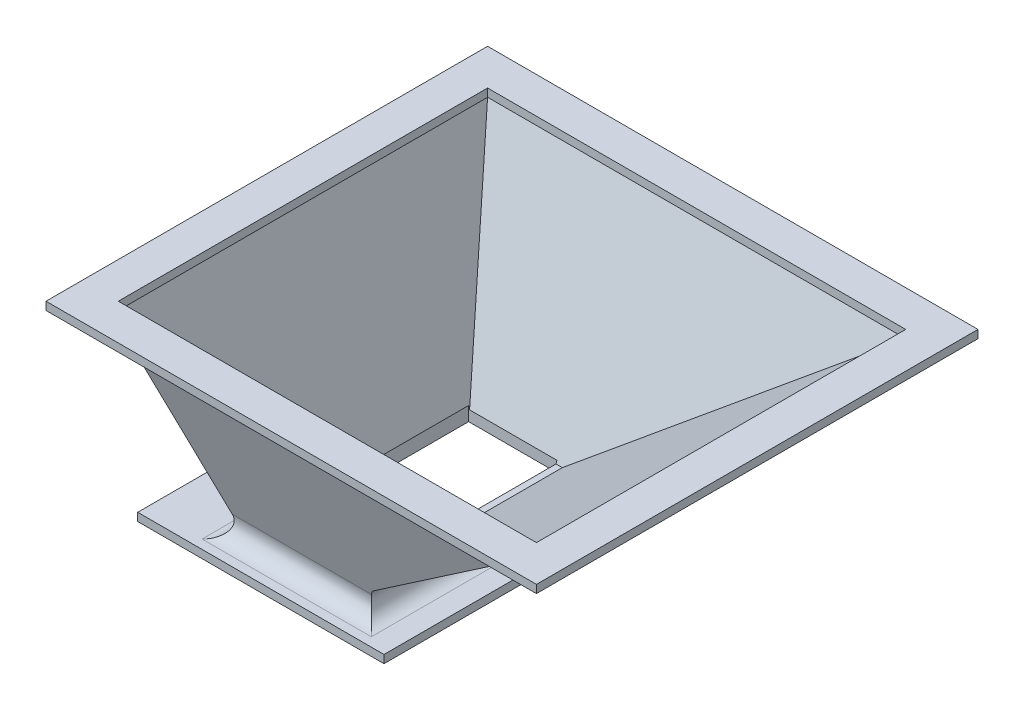
SolidWorks part; units mm, degrees
ref_plane "Front Plane" through (0, 0, 0) normal (0, 0, 1) x (1, 0, 0)
ref_plane "Top Plane" through (0, 0, 0) normal (0, 1, 0) x (1, 0, 0)
ref_plane "Right Plane" through (0, 0, 0) normal (1, 0, 0) x (0, 0, -1)
sketch "Sketch1" plane through (0, 0, 0) normal (0, 1, 0) x (1, 0, 0)
  line L0 (-152.675, 137.475) -> (-152.675, -137.475)
  line L5 (-132.675, 117.475) -> (132.675, 117.475)
  line L6 (-132.675, 117.475) -> (-132.675, -117.475)
  line L7 (-132.675, -117.475) -> (132.675, -117.475)
  line L8 (132.675, 117.475) -> (132.675, -117.475)
  line L9 (-152.675, -137.475) -> (152.675, -137.475)
  line L10 (152.675, 137.475) -> (152.675, -137.475)
  line L11 (-152.675, 137.475) -> (152.675, 137.475)
  line L12 (-130.175, 114.975) -> (-130.175, -114.975)
  line L13 (-130.175, -114.975) -> (130.175, -114.975)
  line L14 (130.175, 114.975) -> (130.175, -114.975)
  line L15 (-130.175, 114.975) -> (130.175, 114.975)
  line L16 (-152.675, 137.475) -> (152.675, -137.475) construction
  point P6 (0, 0)
  point P7 (0, 0)
  point P9 (168.7914, -440.2131)
  point P10 (0, 0)
  dimension "D1" = 20
  dimension "D2" = 2.5
  dimension "D3" = 265.35
  dimension "D4" = 234.95
ref_plane "Plane4" through (0, -133.35, 0) normal (0, 1, 0) x (1, 0, 0)
extrude "Boss-Extrude1" add sketch "Sketch1" along normal blind 5 contours L11 L0 L9 L10 L5 L8 L7 L6 | L8 L5 L6 L7 L12 L15 L14 L13 | L16 L0 L9 L7 L6 L5 | L16 L5 L6 L7 L13 L12 L15 region at (-144.3188, 0, -124.4215) region at (0, 0, -133.366) region at (-131.436, 0, -113.6035) region at (1.1057, 0, -117.1222)
sketch "Sketch2" plane through (0, -133.35, 0) normal (0, 1, 0) x (1, 0, 0)
  line L0 (-94.5, 67.5) -> (-39.5, -67.5) construction
  line L1 (-92, 65) -> (-42, 65)
  line L2 (-92, 65) -> (-92, -65)
  line L3 (-92, -65) -> (-42, -65)
  line L4 (-42, 65) -> (-42, -65)
  line L5 (0, 0) -> (-67, 0) construction
  line L9 (-94.5, 67.5) -> (-94.5, -67.5)
  line L10 (-94.5, -67.5) -> (-39.5, -67.5)
  line L11 (-39.5, 67.5) -> (-39.5, -67.5)
  line L12 (-94.5, 67.5) -> (-39.5, 67.5)
  point P4 (-67, 0)
  point P6 (0, 0)
  point P10 (-67, 65)
  point P13 (-67, 65)
  dimension "D1" = 130
  dimension "D2" = 2.5
  dimension "D3" = 50
  dimension "D4" = 67
loft "Loft1" add section "Sketch1<3>" section "Sketch2" connector at (132.675, 0, 117.475) connector at (-39.5, -133.35, 67.5)
sketch "Sketch1<3>" plane through (0, 0, 0) normal (0, 1, 0) x (1, 0, 0) same geometry as "Sketch1"
loft "Cut-Loft1" cut section "Sketch1<11>" section "Sketch2<5>" connector at (130.175, 0, -114.975) connector at (-42, -133.35, -65)
sketch "Sketch1<11>" plane through (0, 0, 0) normal (0, 1, 0) x (1, 0, 0) same geometry as "Sketch1"
sketch "Sketch2<5>" plane through (0, -133.35, 0) normal (0, 1, 0) x (1, 0, 0) same geometry as "Sketch2"
sketch "Sketch3" plane through (0, -133.35, 0) normal (0, 1, 0) x (1, 0, 0)
  line L0 (-143.675, 89.375) -> (9.675, -89.375) construction
  line L1 (-92, 65) -> (-42, -65) construction
  line L4 (-92, -65) -> (-42, -65) construction
  line L12 (9.675, 89.375) -> (-143.675, 89.375)
  line L13 (-143.675, 89.375) -> (-143.675, -89.375)
  line L14 (-143.675, -89.375) -> (9.675, -89.375)
  line L15 (9.675, -89.375) -> (9.675, 89.375)
  line L17 (-42, 65) -> (-42, -65) construction
  line L18 (-92, 65) -> (-92, -65) construction
  line L19 (-92, 65) -> (-42, 65) construction
  line L20 (-92, -65) -> (-42, -65)
  line L21 (-42, 65) -> (-42, -65)
  line L22 (-92, 65) -> (-92, -65)
  line L23 (-92, 65) -> (-42, 65)
  point P4 (-67, 0)
  point P5 (-67, 0)
  point P7 (0, 0)
  point P9 (0, 0)
  dimension "D1" = 153.35
  dimension "D2" = 178.75
extrude "Boss-Extrude2" add sketch "Sketch3" along normal blind 5 contours L14 L15 L12 L13 L22 L21 | L12 L0 L22 L23 L21 L15 | L0 L13 L14 L21 L20 L22 region at (7.3198, -133.35, 0)
fillet "Fillet1" radius 10 4 edges at (-64.4878, -128.35, -69.3738) (-33.0442, -128.35, 0) (-64.4878, -128.35, 69.3738) (-95.9314, -128.35, 0)
extrude "Cut-Extrude1" cut sketch "Sketch2<6>" along normal blind 10 contours L9 L10 L11 L12
sketch "Sketch2<6>" plane through (0, -133.35, 0) normal (0, 1, 0) x (1, 0, 0) same geometry as "Sketch2"
